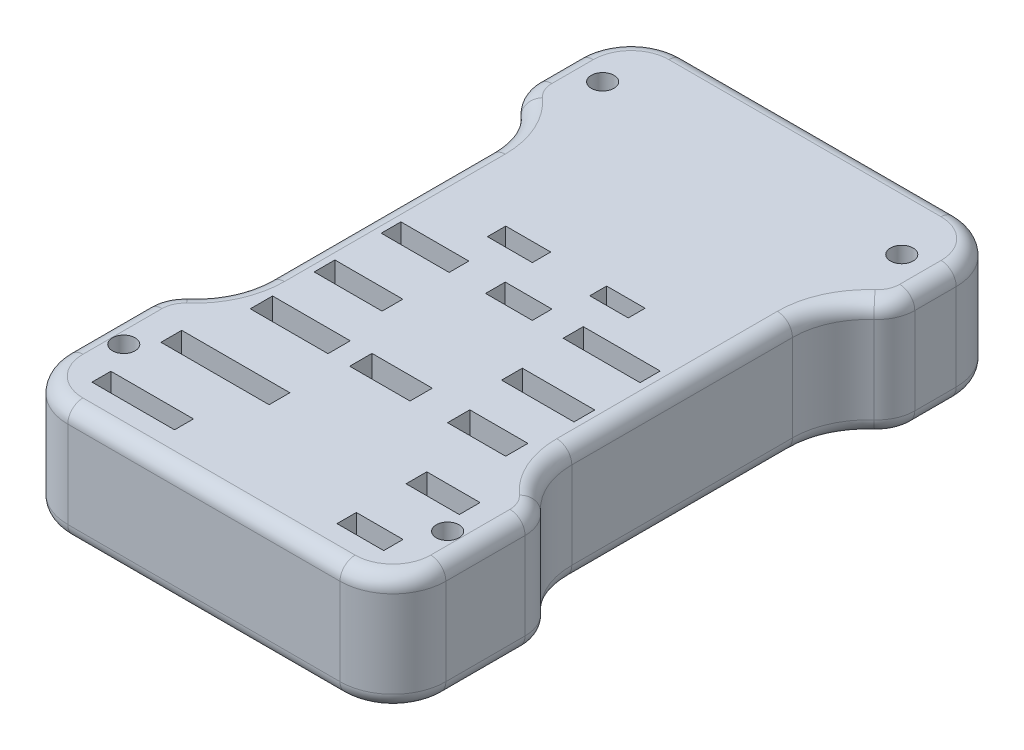
SolidWorks part; units mm, degrees
ref_plane "Front Plane" through (0, 0, 0) normal (0, 0, 1) x (1, 0, 0)
ref_plane "Top Plane" through (0, 0, 0) normal (0, 1, 0) x (1, 0, 0)
ref_plane "Right Plane" through (0, 0, 0) normal (1, 0, 0) x (0, 0, -1)
sketch "Sketch1" plane through (0, 0, 0) normal (0, 1, 0) x (1, 0, 0)
  line L0 (-25, -20.75) -> (25, -20.75) construction
  line L1 (25, -40.75) -> (-25, -40.75)
  line L2 (25, -40.75) -> (25, -20.75)
  line L3 (25, 40.75) -> (-25, 40.75)
  line L4 (-25, -40.75) -> (-25, -20.75)
  line L5 (25, -40.75) -> (-25, 40.75) construction
  line L6 (25, 40.75) -> (-25, -40.75) construction
  line L7 (-25, 25.75) -> (25, 25.75) construction
  line L8 (-20, 40.75) -> (-20, -40.75) construction
  line L9 (20, 40.75) -> (20, -40.75) construction
  line L10 (-25, -20.75) -> (-20, -20.75)
  line L11 (-20, -20.75) -> (-20, 25.75)
  line L12 (-20, 25.75) -> (-25, 25.75)
  line L13 (25, 25.75) -> (20, 25.75)
  line L14 (20, 25.75) -> (20, -20.75)
  line L15 (20, -20.75) -> (25, -20.75)
  line L16 (-25, 25.75) -> (-25, 40.75)
  line L17 (25, 25.75) -> (25, 40.75)
  point P0 (0, 0)
  dimension "D1" = 81.5
  dimension "D2" = 50
  dimension "D3" = 20
  dimension "D4" = 15
  dimension "D5" = 5
  dimension "D6" = 5
extrude "Boss-Extrude1" add sketch "Sketch1" along normal blind 15.5
fillet "Fillet1" radius 7 4 edges at (25, 7.75, -40.75) (-25, 7.75, -40.75) (-25, 7.75, 40.75) (25, 7.75, 40.75)
fillet "Fillet2" radius 10 4 edges at (-20, 7.75, 20.75) (-20, 7.75, -25.75) (20, 7.75, 20.75) (20, 7.75, -25.75)
fillet "Fillet3" radius 5 4 edges at (-25, 7.75, 20.75) (25, 7.75, 20.75) (25, 7.75, -25.75) (-25, 7.75, -25.75)
fillet "Fillet4" radius 2 40 edges at (-22.9497, 0, 38.6997) (0, 0, 40.75) (22.9497, 0, 38.6997) (25, 0, 28.51) (24.5644, 0, 21.2288) (20.8713, 0, 16.1722) (20, 0, -2.5) (20.8713, 0, -21.1722) (24.5644, 0, -26.2288) (25, 0, -31.01) (22.9497, 0, -38.6997) (0, 0, -40.75) (-22.9497, 0, -38.6997) (-25, 0, -31.01) (-24.5644, 0, -26.2288) (-20.8713, 0, -21.1722) (-20, 0, -2.5) (-20.8713, 0, 16.1722) (-24.5644, 0, 21.2288) (-25, 0, 28.51) (-20, 15.5, -2.5) (-20.8713, 15.5, -21.1722) (-24.5644, 15.5, -26.2288) (-25, 15.5, -31.01) (-22.9497, 15.5, -38.6997) (0, 15.5, -40.75) (22.9497, 15.5, -38.6997) (25, 15.5, -31.01) (24.5644, 15.5, -26.2288) (20.8713, 15.5, -21.1722) (20, 15.5, -2.5) (20.8713, 15.5, 16.1722) (24.5644, 15.5, 21.2288) (25, 15.5, 28.51) (22.9497, 15.5, 38.6997) (0, 15.5, 40.75) (-22.9497, 15.5, 38.6997) (-25, 15.5, 28.51) (-24.5644, 15.5, 21.2288) (-20.8713, 15.5, 16.1722)
sketch "Sketch2" plane through (0, 15.5, 0) normal (0, 1, 0) x (1, 0, 0)
  line L1 (-19.2086, -36.344) -> (-8.2858, -36.344)
  line L2 (-19.2086, -36.344) -> (-19.2086, -33.8462)
  line L3 (-19.2086, -33.8462) -> (-8.2858, -33.8462)
  line L4 (-8.2858, -36.344) -> (-8.2858, -33.8462)
  line L5 (-19.2086, -27.2177) -> (-4.9083, -27.2177)
  line L6 (-19.2086, -27.2177) -> (-19.2086, -24.4725)
  line L7 (-19.2086, -24.4725) -> (-4.9083, -24.4725)
  line L8 (-4.9083, -27.2177) -> (-4.9083, -24.4725)
  line L9 (13.2005, -36.344) -> (19.3805, -36.344)
  line L10 (13.2005, -36.344) -> (13.2005, -33.788)
  line L11 (13.2005, -33.788) -> (19.3805, -33.788)
  line L12 (19.3805, -36.344) -> (19.3805, -33.788)
  line L13 (13.2036, -27.2177) -> (20.2485, -27.2177)
  line L14 (13.2036, -27.2177) -> (13.2036, -24.4725)
  line L15 (13.2036, -24.4725) -> (20.2485, -24.4725)
  line L16 (20.2485, -27.2177) -> (20.2485, -24.4725)
  line L17 (-17.1387, -17.4766) -> (-6.8627, -17.4766)
  line L18 (-17.1387, -17.4766) -> (-17.1387, -14.5303)
  line L19 (-17.1387, -14.5303) -> (-6.8627, -14.5303)
  line L20 (-6.8627, -17.4766) -> (-6.8627, -14.5303)
  line L21 (-3.9883, -17.4766) -> (3.9883, -17.4766)
  line L22 (-3.9883, -17.4766) -> (-3.9883, -14.5303)
  line L23 (-3.9883, -14.5303) -> (3.9883, -14.5303)
  line L24 (3.9883, -17.4766) -> (3.9883, -14.5303)
  line L25 (8.9466, -17.4766) -> (16.6357, -17.4766)
  line L26 (8.9466, -17.4766) -> (8.9466, -14.5303)
  line L27 (8.9466, -14.5303) -> (16.6357, -14.5303)
  line L28 (16.6357, -17.4766) -> (16.6357, -14.5303)
  line L29 (-17.1387, -0.1582) -> (-8.1562, -0.1582)
  line L30 (-17.1387, -0.1582) -> (-17.1387, 2.4459)
  line L31 (-17.1387, 2.4459) -> (-8.1562, 2.4459)
  line L32 (-8.1562, -0.1582) -> (-8.1562, 2.4459)
  line L33 (-3.3415, -0.1582) -> (2.8385, -0.1582)
  line L34 (-3.3415, -0.1582) -> (-3.3415, 2.4459)
  line L35 (-3.3415, 2.4459) -> (2.8385, 2.4459)
  line L36 (2.8385, -0.1582) -> (2.8385, 2.4459)
  line L37 (6.9227, -0.1582) -> (17.095, -0.1582)
  line L38 (6.9227, -0.1582) -> (6.9227, 2.5057)
  line L39 (6.9227, 2.5057) -> (17.095, 2.5057)
  line L40 (17.095, -0.1582) -> (17.095, 2.5057)
  line L41 (-9.7229, 6.4688) -> (-3.778, 6.4688)
  line L42 (-9.7229, 6.4688) -> (-9.7229, 8.8962)
  line L43 (-9.7229, 8.8962) -> (-3.778, 8.8962)
  line L44 (-3.778, 6.4688) -> (-3.778, 8.8962)
  line L45 (3.8182, 6.4688) -> (8.9043, 6.4688)
  line L46 (3.8182, 6.4688) -> (3.8182, 8.698)
  line L47 (3.8182, 8.698) -> (8.9043, 8.698)
  line L48 (8.9043, 6.4688) -> (8.9043, 8.698)
  line L49 (-17.1387, -9.028) -> (-8.1562, -9.028)
  line L50 (-17.1387, -9.028) -> (-17.1387, -6.2837)
  line L51 (-17.1387, -6.2837) -> (-8.1562, -6.2837)
  line L52 (-8.1562, -9.028) -> (-8.1562, -6.2837)
  line L53 (7.6493, -9.028) -> (17.2271, -9.028)
  line L54 (7.6493, -9.028) -> (7.6493, -6.2837)
  line L55 (7.6493, -6.2837) -> (17.2271, -6.2837)
  line L56 (17.2271, -9.028) -> (17.2271, -6.2837)
  circle A0 centre (-21.4399, -29.9072) radius 1.5
  circle A1 centre (21.3926, -29.9072) radius 1.5
  circle A2 centre (-19.8384, 31.8246) radius 1.5
  circle A3 centre (19.7237, 31.8246) radius 1.5
  dimension "D1" = 3
extrude "Cut-Extrude1" cut sketch "Sketch2" against normal blind 3.5
sketch "Sketch3" [suppressed] plane through (0, 15.5, 0) normal (0, 1, 0) x (1, 0, 0)
  circle A0 centre (-15.1289, 25.7963) radius 1.5
  circle A1 centre (-15.1289, 20.8069) radius 1.5
  circle A2 centre (15.0296, 26.3714) radius 1.5
  circle A3 centre (15.0296, 21.4862) radius 1.5
  circle A4 centre (15.0296, 16.4365) radius 1.5
  dimension "D1" = 3
extrude "Boss-Extrude2" [suppressed] add sketch "Sketch3" along normal blind 0.1
sketch "Sketch4" [suppressed] plane through (0, 12, 0) normal (0, 1, 0) x (1, 0, 0)
  line L0 (-17.2649, -34.9547) -> (-16.4398, -34.9547)
  line L1 (-18.7649, -34.9547) -> (-17.9398, -34.9547)
  line L2 (-18.7649, -34.9547) -> (-18.7649, -35.7798)
  line L3 (-18.7649, -35.7798) -> (-17.9398, -35.7798)
  line L4 (-17.9398, -34.9547) -> (-17.9398, -35.7798)
  line L5 (-18.7649, -34.9547) -> (-17.9398, -35.7798) construction
  line L6 (-18.7649, -35.7798) -> (-17.9398, -34.9547) construction
  line L7 (-16.4398, -34.9547) -> (-16.4398, -35.7798)
  line L8 (-17.2649, -34.9547) -> (-17.2649, -35.7798)
  line L9 (-17.2649, -35.7798) -> (-16.4398, -35.7798)
  line L10 (-15.7649, -34.9547) -> (-14.9398, -34.9547)
  line L11 (-14.9398, -34.9547) -> (-14.9398, -35.7798)
  line L12 (-15.7649, -34.9547) -> (-15.7649, -35.7798)
  line L13 (-15.7649, -35.7798) -> (-14.9398, -35.7798)
  line L14 (-14.2649, -34.9547) -> (-13.4398, -34.9547)
  line L15 (-13.4398, -34.9547) -> (-13.4398, -35.7798)
  line L16 (-14.2649, -34.9547) -> (-14.2649, -35.7798)
  line L17 (-14.2649, -35.7798) -> (-13.4398, -35.7798)
  line L18 (-12.7649, -34.9547) -> (-11.9398, -34.9547)
  line L19 (-11.9398, -34.9547) -> (-11.9398, -35.7798)
  line L20 (-12.7649, -34.9547) -> (-12.7649, -35.7798)
  line L21 (-12.7649, -35.7798) -> (-11.9398, -35.7798)
  line L22 (-11.2649, -34.9547) -> (-10.4398, -34.9547)
  line L23 (-10.4398, -34.9547) -> (-10.4398, -35.7798)
  line L24 (-11.2649, -34.9547) -> (-11.2649, -35.7798)
  line L25 (-11.2649, -35.7798) -> (-10.4398, -35.7798)
  line L26 (-9.7649, -34.9547) -> (-8.9398, -34.9547)
  line L27 (-8.9398, -34.9547) -> (-8.9398, -35.7798)
  line L28 (-9.7649, -34.9547) -> (-9.7649, -35.7798)
  line L29 (-9.7649, -35.7798) -> (-8.9398, -35.7798)
  line L30 (14.3718, -34.8507) -> (15.1968, -34.8507)
  line L31 (15.1968, -34.8507) -> (15.1968, -35.6758)
  line L32 (14.3718, -34.8507) -> (14.3718, -35.6758)
  line L33 (14.3718, -35.6758) -> (15.1968, -35.6758)
  line L34 (15.8718, -34.8507) -> (16.6968, -34.8507)
  line L35 (16.6968, -34.8507) -> (16.6968, -35.6758)
  line L36 (15.8718, -34.8507) -> (15.8718, -35.6758)
  line L37 (15.8718, -35.6758) -> (16.6968, -35.6758)
  line L38 (17.3718, -34.8507) -> (18.1968, -34.8507)
  line L39 (18.1968, -34.8507) -> (18.1968, -35.6758)
  line L40 (17.3718, -34.8507) -> (17.3718, -35.6758)
  line L41 (17.3718, -35.6758) -> (18.1968, -35.6758)
  line L42 (13.9552, -25.9196) -> (14.7803, -25.9196)
  line L43 (14.7803, -25.9196) -> (14.7803, -26.7446)
  line L44 (13.9552, -25.9196) -> (13.9552, -26.7446)
  line L45 (13.9552, -26.7446) -> (14.7803, -26.7446)
  line L46 (15.4552, -25.9196) -> (16.2803, -25.9196)
  line L47 (16.2803, -25.9196) -> (16.2803, -26.7446)
  line L48 (15.4552, -25.9196) -> (15.4552, -26.7446)
  line L49 (15.4552, -26.7446) -> (16.2803, -26.7446)
  line L50 (16.9552, -25.9196) -> (17.7803, -25.9196)
  line L51 (17.7803, -25.9196) -> (17.7803, -26.7446)
  line L52 (16.9552, -25.9196) -> (16.9552, -26.7446)
  line L53 (16.9552, -26.7446) -> (17.7803, -26.7446)
  line L54 (18.4552, -25.9196) -> (19.2803, -25.9196)
  line L55 (19.2803, -25.9196) -> (19.2803, -26.7446)
  line L56 (18.4552, -25.9196) -> (18.4552, -26.7446)
  line L57 (18.4552, -26.7446) -> (19.2803, -26.7446)
  line L58 (-18.5073, -25.9733) -> (-17.6822, -25.9733)
  line L59 (-17.6822, -25.9733) -> (-17.6822, -26.7984)
  line L60 (-18.5073, -25.9733) -> (-18.5073, -26.7984)
  line L61 (-18.5073, -26.7984) -> (-17.6822, -26.7984)
  line L62 (-17.0073, -25.9733) -> (-16.1822, -25.9733)
  line L63 (-16.1822, -25.9733) -> (-16.1822, -26.7984)
  line L64 (-17.0073, -25.9733) -> (-17.0073, -26.7984)
  line L65 (-17.0073, -26.7984) -> (-16.1822, -26.7984)
  line L66 (-15.5073, -25.9733) -> (-14.6822, -25.9733)
  line L67 (-14.6822, -25.9733) -> (-14.6822, -26.7984)
  line L68 (-15.5073, -25.9733) -> (-15.5073, -26.7984)
  line L69 (-15.5073, -26.7984) -> (-14.6822, -26.7984)
  line L70 (-14.0073, -25.9733) -> (-13.1822, -25.9733)
  line L71 (-13.1822, -25.9733) -> (-13.1822, -26.7984)
  line L72 (-14.0073, -25.9733) -> (-14.0073, -26.7984)
  line L73 (-14.0073, -26.7984) -> (-13.1822, -26.7984)
  line L74 (-12.5073, -25.9733) -> (-11.6822, -25.9733)
  line L75 (-11.6822, -25.9733) -> (-11.6822, -26.7984)
  line L76 (-12.5073, -25.9733) -> (-12.5073, -26.7984)
  line L77 (-12.5073, -26.7984) -> (-11.6822, -26.7984)
  line L78 (-11.0073, -25.9733) -> (-10.1822, -25.9733)
  line L79 (-10.1822, -25.9733) -> (-10.1822, -26.7984)
  line L80 (-11.0073, -25.9733) -> (-11.0073, -26.7984)
  line L81 (-11.0073, -26.7984) -> (-10.1822, -26.7984)
  line L82 (-9.5073, -25.9733) -> (-8.6822, -25.9733)
  line L83 (-8.6822, -25.9733) -> (-8.6822, -26.7984)
  line L84 (-9.5073, -25.9733) -> (-9.5073, -26.7984)
  line L85 (-9.5073, -26.7984) -> (-8.6822, -26.7984)
  line L86 (-8.0073, -25.9733) -> (-7.1822, -25.9733)
  line L87 (-7.1822, -25.9733) -> (-7.1822, -26.7984)
  line L88 (-8.0073, -25.9733) -> (-8.0073, -26.7984)
  line L89 (-8.0073, -26.7984) -> (-7.1822, -26.7984)
  line L90 (-6.5073, -25.9733) -> (-5.6822, -25.9733)
  line L91 (-5.6822, -25.9733) -> (-5.6822, -26.7984)
  line L92 (-6.5073, -25.9733) -> (-6.5073, -26.7984)
  line L93 (-6.5073, -26.7984) -> (-5.6822, -26.7984)
  line L94 (-14.9189, -16.2812) -> (-14.0939, -16.2812)
  line L95 (-14.0939, -16.2812) -> (-14.0939, -17.1062)
  line L96 (-14.9189, -16.2812) -> (-14.9189, -17.1062)
  line L97 (-14.9189, -17.1062) -> (-14.0939, -17.1062)
  line L98 (-13.4189, -16.2812) -> (-12.5939, -16.2812)
  line L99 (-12.5939, -16.2812) -> (-12.5939, -17.1062)
  line L100 (-13.4189, -16.2812) -> (-13.4189, -17.1062)
  line L101 (-13.4189, -17.1062) -> (-12.5939, -17.1062)
  line L102 (-11.9189, -16.2812) -> (-11.0939, -16.2812)
  line L103 (-11.0939, -16.2812) -> (-11.0939, -17.1062)
  line L104 (-11.9189, -16.2812) -> (-11.9189, -17.1062)
  line L105 (-11.9189, -17.1062) -> (-11.0939, -17.1062)
  line L106 (-10.4189, -16.2812) -> (-9.5939, -16.2812)
  line L107 (-9.5939, -16.2812) -> (-9.5939, -17.1062)
  line L108 (-10.4189, -16.2812) -> (-10.4189, -17.1062)
  line L109 (-10.4189, -17.1062) -> (-9.5939, -17.1062)
  line L110 (-1.8938, -16.2729) -> (-1.0688, -16.2729)
  line L111 (-3.3938, -16.2729) -> (-2.5688, -16.2729)
  line L112 (-3.3938, -16.2729) -> (-3.3938, -17.0979)
  line L113 (-3.3938, -17.0979) -> (-2.5688, -17.0979)
  line L114 (-2.5688, -16.2729) -> (-2.5688, -17.0979)
  line L115 (-3.3938, -16.2729) -> (-2.5688, -17.0979) construction
  line L116 (-3.3938, -17.0979) -> (-2.5688, -16.2729) construction
  line L117 (-1.0688, -16.2729) -> (-1.0688, -17.0979)
  line L118 (-1.8938, -16.2729) -> (-1.8938, -17.0979)
  line L119 (-1.8938, -17.0979) -> (-1.0688, -17.0979)
  line L120 (-0.3938, -16.2729) -> (0.4312, -16.2729)
  line L121 (0.4312, -16.2729) -> (0.4312, -17.0979)
  line L122 (-0.3938, -16.2729) -> (-0.3938, -17.0979)
  line L123 (-0.3938, -17.0979) -> (0.4312, -17.0979)
  line L124 (1.1062, -16.2729) -> (1.9312, -16.2729)
  line L125 (1.9312, -16.2729) -> (1.9312, -17.0979)
  line L126 (1.1062, -16.2729) -> (1.1062, -17.0979)
  line L127 (1.1062, -17.0979) -> (1.9312, -17.0979)
  line L128 (2.6062, -16.2729) -> (3.4312, -16.2729)
  line L129 (3.4312, -16.2729) -> (3.4312, -17.0979)
  line L130 (2.6062, -16.2729) -> (2.6062, -17.0979)
  line L131 (2.6062, -17.0979) -> (3.4312, -17.0979)
  line L132 (9.8768, -16.2729) -> (10.7019, -16.2729)
  line L133 (10.7019, -16.2729) -> (10.7019, -17.0979)
  line L134 (9.8768, -16.2729) -> (9.8768, -17.0979)
  line L135 (9.8768, -17.0979) -> (10.7019, -17.0979)
  line L136 (11.3768, -16.2729) -> (12.2019, -16.2729)
  line L137 (12.2019, -16.2729) -> (12.2019, -17.0979)
  line L138 (11.3768, -16.2729) -> (11.3768, -17.0979)
  line L139 (11.3768, -17.0979) -> (12.2019, -17.0979)
  line L140 (12.8768, -16.2729) -> (13.7019, -16.2729)
  line L141 (13.7019, -16.2729) -> (13.7019, -17.0979)
  line L142 (12.8768, -16.2729) -> (12.8768, -17.0979)
  line L143 (12.8768, -17.0979) -> (13.7019, -17.0979)
  line L144 (14.3768, -16.2729) -> (15.2019, -16.2729)
  line L145 (15.2019, -16.2729) -> (15.2019, -17.0979)
  line L146 (14.3768, -16.2729) -> (14.3768, -17.0979)
  line L147 (14.3768, -17.0979) -> (15.2019, -17.0979)
  line L148 (8.1299, -7.9213) -> (8.9549, -7.9213)
  line L149 (8.9549, -7.9213) -> (8.9549, -8.7464)
  line L150 (8.1299, -7.9213) -> (8.1299, -8.7464)
  line L151 (8.1299, -8.7464) -> (8.9549, -8.7464)
  line L152 (9.6299, -7.9213) -> (10.4549, -7.9213)
  line L153 (10.4549, -7.9213) -> (10.4549, -8.7464)
  line L154 (9.6299, -7.9213) -> (9.6299, -8.7464)
  line L155 (9.6299, -8.7464) -> (10.4549, -8.7464)
  line L156 (11.1299, -7.9213) -> (11.9549, -7.9213)
  line L157 (11.9549, -7.9213) -> (11.9549, -8.7464)
  line L158 (11.1299, -7.9213) -> (11.1299, -8.7464)
  line L159 (11.1299, -8.7464) -> (11.9549, -8.7464)
  line L160 (12.6299, -7.9213) -> (13.4549, -7.9213)
  line L161 (13.4549, -7.9213) -> (13.4549, -8.7464)
  line L162 (12.6299, -7.9213) -> (12.6299, -8.7464)
  line L163 (12.6299, -8.7464) -> (13.4549, -8.7464)
  line L164 (14.1299, -7.9213) -> (14.9549, -7.9213)
  line L165 (14.9549, -7.9213) -> (14.9549, -8.7464)
  line L166 (14.1299, -7.9213) -> (14.1299, -8.7464)
  line L167 (14.1299, -8.7464) -> (14.9549, -8.7464)
  line L168 (15.6299, -7.9213) -> (16.4549, -7.9213)
  line L169 (16.4549, -7.9213) -> (16.4549, -8.7464)
  line L170 (15.6299, -7.9213) -> (15.6299, -8.7464)
  line L171 (15.6299, -8.7464) -> (16.4549, -8.7464)
  line L172 (-16.8346, -7.8267) -> (-16.0095, -7.8267)
  line L173 (-16.0095, -7.8267) -> (-16.0095, -8.6518)
  line L174 (-16.8346, -7.8267) -> (-16.8346, -8.6518)
  line L175 (-16.8346, -8.6518) -> (-16.0095, -8.6518)
  line L176 (-15.3346, -7.8267) -> (-14.5095, -7.8267)
  line L177 (-14.5095, -7.8267) -> (-14.5095, -8.6518)
  line L178 (-15.3346, -7.8267) -> (-15.3346, -8.6518)
  line L179 (-15.3346, -8.6518) -> (-14.5095, -8.6518)
  line L180 (-13.8346, -7.8267) -> (-13.0095, -7.8267)
  line L181 (-13.0095, -7.8267) -> (-13.0095, -8.6518)
  line L182 (-13.8346, -7.8267) -> (-13.8346, -8.6518)
  line L183 (-13.8346, -8.6518) -> (-13.0095, -8.6518)
  line L184 (-12.3346, -7.8267) -> (-11.5095, -7.8267)
  line L185 (-11.5095, -7.8267) -> (-11.5095, -8.6518)
  line L186 (-12.3346, -7.8267) -> (-12.3346, -8.6518)
  line L187 (-12.3346, -8.6518) -> (-11.5095, -8.6518)
  line L188 (-10.8346, -7.8267) -> (-10.0095, -7.8267)
  line L189 (-10.0095, -7.8267) -> (-10.0095, -8.6518)
  line L190 (-10.8346, -7.8267) -> (-10.8346, -8.6518)
  line L191 (-10.8346, -8.6518) -> (-10.0095, -8.6518)
  line L192 (-9.3346, -7.8267) -> (-8.5095, -7.8267)
  line L193 (-8.5095, -7.8267) -> (-8.5095, -8.6518)
  line L194 (-9.3346, -7.8267) -> (-9.3346, -8.6518)
  line L195 (-9.3346, -8.6518) -> (-8.5095, -8.6518)
  line L196 (-16.8346, 1.1359) -> (-16.0095, 1.1359)
  line L197 (-16.0095, 1.1359) -> (-16.0095, 0.3109)
  line L198 (-16.8346, 1.1359) -> (-16.8346, 0.3109)
  line L199 (-16.8346, 0.3109) -> (-16.0095, 0.3109)
  line L200 (-15.3346, 1.1359) -> (-14.5095, 1.1359)
  line L201 (-14.5095, 1.1359) -> (-14.5095, 0.3109)
  line L202 (-15.3346, 1.1359) -> (-15.3346, 0.3109)
  line L203 (-15.3346, 0.3109) -> (-14.5095, 0.3109)
  line L204 (-13.8346, 1.1359) -> (-13.0095, 1.1359)
  line L205 (-13.0095, 1.1359) -> (-13.0095, 0.3109)
  line L206 (-13.8346, 1.1359) -> (-13.8346, 0.3109)
  line L207 (-13.8346, 0.3109) -> (-13.0095, 0.3109)
  line L208 (-12.3346, 1.1359) -> (-11.5095, 1.1359)
  line L209 (-11.5095, 1.1359) -> (-11.5095, 0.3109)
  line L210 (-12.3346, 1.1359) -> (-12.3346, 0.3109)
  line L211 (-12.3346, 0.3109) -> (-11.5095, 0.3109)
  line L212 (-10.8346, 1.1359) -> (-10.0095, 1.1359)
  line L213 (-10.0095, 1.1359) -> (-10.0095, 0.3109)
  line L214 (-10.8346, 1.1359) -> (-10.8346, 0.3109)
  line L215 (-10.8346, 0.3109) -> (-10.0095, 0.3109)
  line L216 (-9.3346, 1.1359) -> (-8.5095, 1.1359)
  line L217 (-8.5095, 1.1359) -> (-8.5095, 0.3109)
  line L218 (-9.3346, 1.1359) -> (-9.3346, 0.3109)
  line L219 (-9.3346, 0.3109) -> (-8.5095, 0.3109)
  line L220 (8.0944, 1.0811) -> (8.9195, 1.0811)
  line L221 (8.9195, 1.0811) -> (8.9195, 0.2561)
  line L222 (8.0944, 1.0811) -> (8.0944, 0.2561)
  line L223 (8.0944, 0.2561) -> (8.9195, 0.2561)
  line L224 (9.5944, 1.0811) -> (10.4195, 1.0811)
  line L225 (10.4195, 1.0811) -> (10.4195, 0.2561)
  line L226 (9.5944, 1.0811) -> (9.5944, 0.2561)
  line L227 (9.5944, 0.2561) -> (10.4195, 0.2561)
  line L228 (11.0944, 1.0811) -> (11.9195, 1.0811)
  line L229 (11.9195, 1.0811) -> (11.9195, 0.2561)
  line L230 (11.0944, 1.0811) -> (11.0944, 0.2561)
  line L231 (11.0944, 0.2561) -> (11.9195, 0.2561)
  line L232 (12.5944, 1.0811) -> (13.4195, 1.0811)
  line L233 (13.4195, 1.0811) -> (13.4195, 0.2561)
  line L234 (12.5944, 1.0811) -> (12.5944, 0.2561)
  line L235 (12.5944, 0.2561) -> (13.4195, 0.2561)
  line L236 (14.0944, 1.0811) -> (14.9195, 1.0811)
  line L237 (14.9195, 1.0811) -> (14.9195, 0.2561)
  line L238 (14.0944, 1.0811) -> (14.0944, 0.2561)
  line L239 (14.0944, 0.2561) -> (14.9195, 0.2561)
  line L240 (15.5944, 1.0811) -> (16.4195, 1.0811)
  line L241 (16.4195, 1.0811) -> (16.4195, 0.2561)
  line L242 (15.5944, 1.0811) -> (15.5944, 0.2561)
  line L243 (15.5944, 0.2561) -> (16.4195, 0.2561)
  line L244 (-2.3314, 1.3286) -> (-1.5064, 1.3286)
  line L245 (-1.5064, 1.3286) -> (-1.5064, 0.5035)
  line L246 (-2.3314, 1.3286) -> (-2.3314, 0.5035)
  line L247 (-2.3314, 0.5035) -> (-1.5064, 0.5035)
  line L248 (-0.8314, 1.3286) -> (-0.0064, 1.3286)
  line L249 (-0.0064, 1.3286) -> (-0.0064, 0.5035)
  line L250 (-0.8314, 1.3286) -> (-0.8314, 0.5035)
  line L251 (-0.8314, 0.5035) -> (-0.0064, 0.5035)
  line L252 (0.6686, 1.3286) -> (1.4936, 1.3286)
  line L253 (1.4936, 1.3286) -> (1.4936, 0.5035)
  line L254 (0.6686, 1.3286) -> (0.6686, 0.5035)
  line L255 (0.6686, 0.5035) -> (1.4936, 0.5035)
  line L256 (-8.8055, 7.6958) -> (-7.9805, 7.6958)
  line L257 (-7.9805, 7.6958) -> (-7.9805, 6.8708)
  line L258 (-8.8055, 7.6958) -> (-8.8055, 6.8708)
  line L259 (-8.8055, 6.8708) -> (-7.9805, 6.8708)
  line L260 (-7.3055, 7.6958) -> (-6.4805, 7.6958)
  line L261 (-6.4805, 7.6958) -> (-6.4805, 6.8708)
  line L262 (-7.3055, 7.6958) -> (-7.3055, 6.8708)
  line L263 (-7.3055, 6.8708) -> (-6.4805, 6.8708)
  line L264 (-5.8055, 7.6958) -> (-4.9805, 7.6958)
  line L265 (-4.9805, 7.6958) -> (-4.9805, 6.8708)
  line L266 (-5.8055, 7.6958) -> (-5.8055, 6.8708)
  line L267 (-5.8055, 6.8708) -> (-4.9805, 6.8708)
  line L268 (5.1061, 7.6665) -> (5.9311, 7.6665)
  line L269 (5.9311, 7.6665) -> (5.9311, 6.8415)
  line L270 (5.1061, 7.6665) -> (5.1061, 6.8415)
  line L271 (5.1061, 6.8415) -> (5.9311, 6.8415)
  line L272 (6.6061, 7.6665) -> (7.4311, 7.6665)
  line L273 (7.4311, 7.6665) -> (7.4311, 6.8415)
  line L274 (6.6061, 7.6665) -> (6.6061, 6.8415)
  line L275 (6.6061, 6.8415) -> (7.4311, 6.8415)
  point P0 (-18.3523, -35.3672)
  dimension "D2" = 9
  dimension "D1" = 7
extrude "Boss-Extrude3" [suppressed] add sketch "Sketch4" along normal blind 3
sketch "Sketch5" [suppressed] plane through (0, 12, 0) normal (0, 1, 0) x (1, 0, 0)
  circle A0 centre (-19.8384, 31.8246) radius 1.5
  circle A1 centre (19.7237, 31.8246) radius 1.5
  circle A2 centre (21.3926, -29.9072) radius 1.5
  circle A3 centre (-21.3384, -29.9072) radius 1.6015
extrude "Boss-Extrude4" [suppressed] add sketch "Sketch5" along normal blind 4
sketch "Sketch6" [suppressed] plane through (0, 16, 0) normal (0, 1, 0) x (1, 0, 0)
  line L1 (-21.4153, -28.3922) -> (-21.2395, -28.3922)
  line L2 (-21.4153, -28.3922) -> (-21.4153, -31.3814)
  line L3 (-21.4153, -31.3814) -> (-21.2395, -31.3814)
  line L4 (-21.2395, -28.3922) -> (-21.2395, -31.3814)
  line L5 (-19.8606, -30.021) -> (-22.859, -30.021)
  line L6 (-19.8606, -30.021) -> (-19.8606, -29.8868)
  line L7 (-19.8606, -29.8868) -> (-22.859, -29.8868)
  line L8 (-22.859, -30.021) -> (-22.859, -29.8868)
  line L9 (20.0826, -29.9539) -> (22.7499, -29.9539)
  line L10 (20.0826, -29.9539) -> (20.0826, -29.7866)
  line L11 (20.0826, -29.7866) -> (22.7499, -29.7866)
  line L12 (22.7499, -29.9539) -> (22.7499, -29.7866)
  line L13 (21.2931, -28.4904) -> (21.5501, -28.4904)
  line L14 (21.2931, -28.4904) -> (21.2931, -31.2112)
  line L15 (21.2931, -31.2112) -> (21.5501, -31.2112)
  line L16 (21.5501, -28.4904) -> (21.5501, -31.2112)
  line L17 (19.6238, 33.245) -> (19.8439, 33.245)
  line L18 (19.6238, 33.245) -> (19.6238, 30.4232)
  line L19 (19.6238, 30.4232) -> (19.8439, 30.4232)
  line L20 (19.8439, 33.245) -> (19.8439, 30.4232)
  line L21 (21.0847, 31.664) -> (18.323, 31.664)
  line L22 (21.0847, 31.664) -> (21.0847, 31.9342)
  line L23 (21.0847, 31.9342) -> (18.323, 31.9342)
  line L24 (18.323, 31.664) -> (18.323, 31.9342)
  line L25 (-19.9995, 33.245) -> (-19.7369, 33.245)
  line L26 (-19.9995, 33.245) -> (-19.9995, 30.4232)
  line L27 (-19.9995, 30.4232) -> (-19.7369, 30.4232)
  line L28 (-19.7369, 33.245) -> (-19.7369, 30.4232)
  line L29 (-18.5114, 31.5705) -> (-21.2395, 31.5705)
  line L30 (-18.5114, 31.5705) -> (-18.5114, 31.8341)
  line L31 (-18.5114, 31.8341) -> (-21.2395, 31.8341)
  line L32 (-21.2395, 31.5705) -> (-21.2395, 31.8341)
extrude "Cut-Extrude2" [suppressed] cut sketch "Sketch6" against normal blind 0.5 contours L28 L27 L26 L25 | L4 L3 L2 L1 | L5 L8 L7 L6 | L9 L12 L11 L10 | L16 L15 L14 L13 | L21 L24 L23 L22 | L20 L19 L18 L17 | L29 L32 L31 L30
fillet "Fillet6" [suppressed] radius 0.2
fillet "Fillet7" [suppressed] radius 0.2
